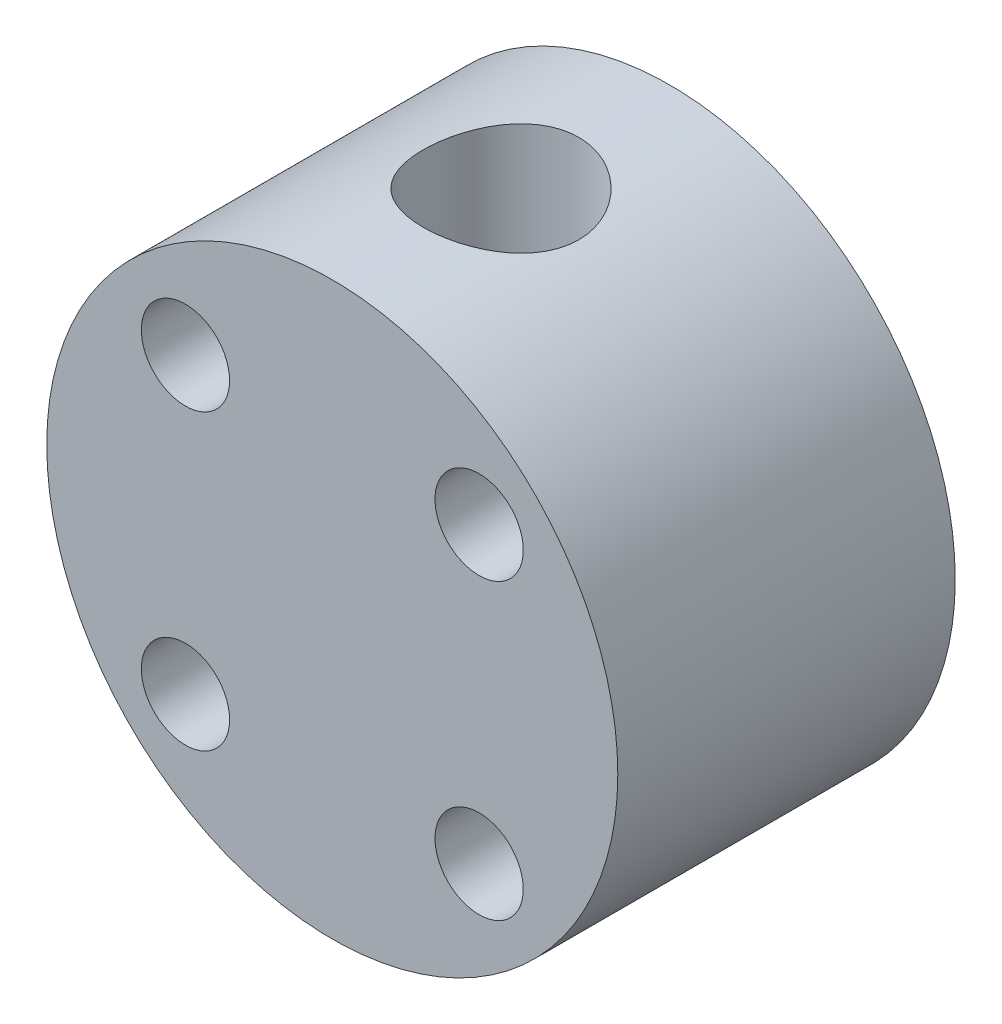
SolidWorks part; units mm, degrees
material "ABS"
ref_plane "Front Plane" through (0, 0, 0) normal (0, 0, 1) x (1, 0, 0)
ref_plane "Top Plane" through (0, 0, 0) normal (0, 1, 0) x (1, 0, 0)
ref_plane "Right Plane" through (0, 0, 0) normal (1, 0, 0) x (0, 0, -1)
sketch "Sketch1" plane through (0, 0, 0) normal (0, 0, 1) x (1, 0, 0)
  circle A0 centre (0, 0) radius 11
  dimension "D1" = 22
extrude "Boss-Extrude1" add sketch "Sketch1" along normal mid plane 13
sketch "Sketch2" plane through (0, 0, 0) normal (0, 1, 0) x (1, 0, 0)
  circle A0 centre (0, 0) radius 3
  dimension "D1" = 6
extrude "Cut-Extrude1" cut sketch "Sketch2" against normal through all both and the other way through all
hole_wizard "M3 Clearance Hole1" positions "Sketch3" profile "Sketch4" hole size "M3" standard "ANSI Metric" end condition up to next
sketch "Sketch3" plane through (0, 0, 6.5) normal (0, 0, 1) x (1, 0, 0)
  line L1 (-5.6569, -5.6569) -> (5.6569, -5.6569) construction
  line L2 (-5.6569, -5.6569) -> (-5.6569, 5.6569) construction
  line L3 (-5.6569, 5.6569) -> (5.6569, 5.6569) construction
  line L4 (5.6569, -5.6569) -> (5.6569, 5.6569) construction
  line L5 (-5.6569, -5.6569) -> (5.6569, 5.6569) construction
  line L6 (-5.6569, 5.6569) -> (5.6569, -5.6569) construction
  point P2 (5.6569, 5.6569)
  point P37 (-5.6569, -5.6569)
  point P38 (-5.6569, 5.6569)
  point P39 (5.6569, -5.6569)
  dimension "D1" = 16
sketch "Sketch4" plane through (5.6569, 5.6569, 6.5) normal (1, 0, 0) x (0, -1, 0)
  line L0 (0, 0) -> (0, 13)
  line L1 (0, 13) -> (1.7, 13)
  line L2 (1.7, 13) -> (1.7, 0)
  line L5 (1.7, 0) -> (0, 0)
  line L11 (0, -6.35) -> (0, 107.95) construction
  dimension "Thru Hole Dia." = 3.4
  dimension "Thru Hole Depth" = 13
